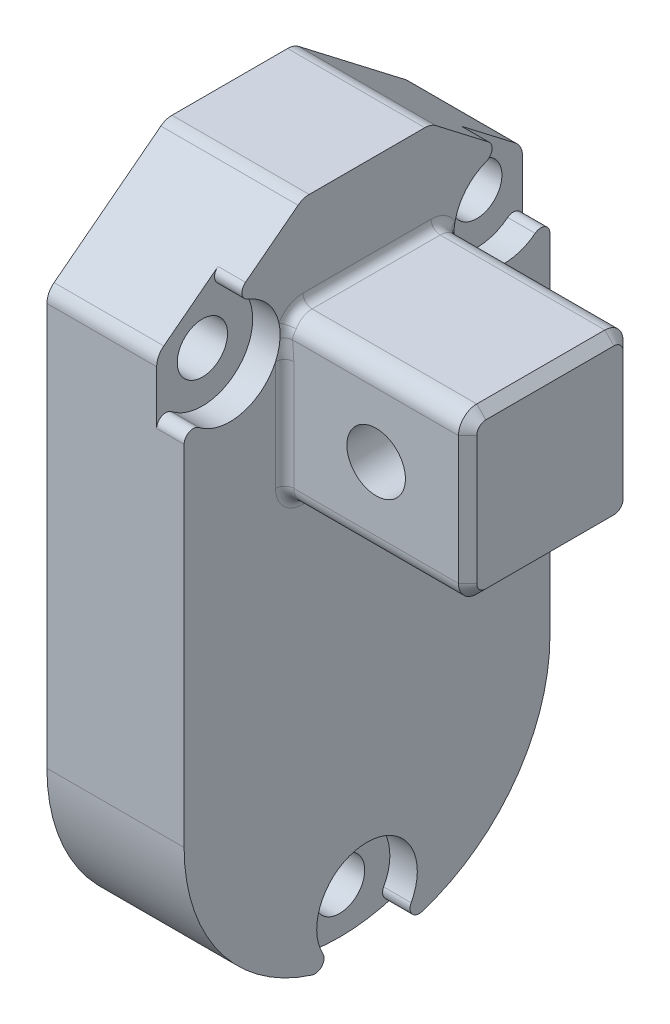
SolidWorks part; units mm, degrees
ref_plane "Ebene vorne" through (0, 0, 0) normal (0, 0, 1) x (1, 0, 0)
ref_plane "Ebene oben" through (0, 0, 0) normal (0, 1, 0) x (1, 0, 0)
ref_plane "Ebene rechts" through (0, 0, 0) normal (1, 0, 0) x (0, 0, -1)
sketch "Skizze1" plane through (0, 0, 0) normal (1, 0, 0) x (0, 0, -1)
  line L0 (0, 0) -> (0, 55) construction
  line L2 (-20, 0) -> (-20, 45)
  line L3 (-7, 55) -> (7, 55)
  line L4 (20, 0) -> (20, 45)
  line L5 (-20, 45) -> (-7, 55)
  line L6 (7, 55) -> (20, 45)
  arc A0 (-20, 0) -> (20, 0) centre (0, 0) ccw
  point P4 (0, 55)
  dimension "D1" = 40
  dimension "D2" = 75
  dimension "D3" = 10
  dimension "D4" = 13
extrude "Aufsatz-Linear austragen1" add sketch "Skizze1" along normal blind 15
hole_wizard "Stirnsenkung für M5 Flachkopfschraube mit Schlitz4" positions "Skizze4" profile "Skizze3" counterbore size "M5" standard "ISO" end condition up to next
sketch "Skizze4" plane through (15, 0, 0) normal (1, 0, 0) x (0, 0, -1)
  line L0 (0, -15) -> (0, 36.0253) construction
  point P0 (0, -15)
  point P2 (15, 43.3)
  point P4 (-15, 43.3)
  dimension "D1" = 15
  dimension "D2" = 30
  dimension "D3" = 58.3
sketch "Skizze3" plane through (15, -15, 0) normal (0, 1, 0) x (0, 0, -1)
  line L0 (0, 0) -> (0, 15)
  line L1 (0, 15) -> (2.75, 15)
  line L3 (2.75, 15) -> (2.75, 3)
  line L4 (2.75, 3) -> (5.5, 3)
  line L5 (5.5, 3) -> (5.5, 0)
  line L7 (5.5, 0) -> (0, 0)
  line L11 (0, -6.35) -> (0, 107.95) construction
  dimension "Bohrerdurchmesser" = 5.5
  dimension "Bohrungstiefe" = 15
  dimension "Senkdurchmesser2" = 11
  dimension "Senktiefe2" = 3
fillet "Verrundung1" radius 1 6 edges at (13.5, 48.7997, 15.0604) (13.5, 41.0087, 20) (13.5, 41.0087, -20) (13.5, 48.7997, -15.0604) (13.5, -19.825, -2.64) (13.5, -19.825, 2.64)
fillet "Verrundung2" radius 2 4 edges at (6, 45, -20) (7.5, 55, -7) (7.5, 55, 7) (6, 45, 20)
sketch "Skizze5" plane through (15, 0, 0) normal (1, 0, 0) x (0, 0, -1)
  line L0 (6.3198, 55) -> (-6.3198, 55) construction
  line L1 (-9, 45) -> (9, 45)
  line L2 (-9, 45) -> (-9, 27)
  line L3 (-9, 27) -> (9, 27)
  line L4 (9, 45) -> (9, 27)
  line L5 (-9, 45) -> (9, 27) construction
  line L6 (-9, 27) -> (9, 45) construction
  point P0 (0, 36)
  dimension "D1" = 18
  dimension "D2" = 19
extrude "Aufsatz-Linear austragen2" add sketch "Skizze5" along normal blind 20
sketch "Skizze6" plane through (0, 0, -9) normal (0, 0, -1) x (-1, 0, 0)
  line L0 (-15, 45) -> (-35, 27) construction
  circle A0 centre (-25, 36) radius 3.2
  dimension "D1" = 6.4
extrude "Schnitt-Linear austragen1" cut sketch "Skizze6" against normal up to next
fillet "Verrundung3" radius 2 4 edges at (25, 27, -9) (25, 45, -9) (25, 27, 9) (25, 45, 9)
chamfer "Fase1" distance 1 angle 45 8 edges at (35, 27, 0) (35, 27.5858, -8.4142) (35, 27.5858, 8.4142) (35, 36, -9) (35, 36, 9) (35, 44.4142, -8.4142) (35, 44.4142, 8.4142) (35, 45, 0)
fillet "Verrundung4" radius 1 8 edges at (15, 27.5858, -8.4142) (15, 27, 0) (15, 27.5858, 8.4142) (15, 36, 9) (15, 44.4142, 8.4142) (15, 45, 0) (15, 44.4142, -8.4142) (15, 36, -9)
